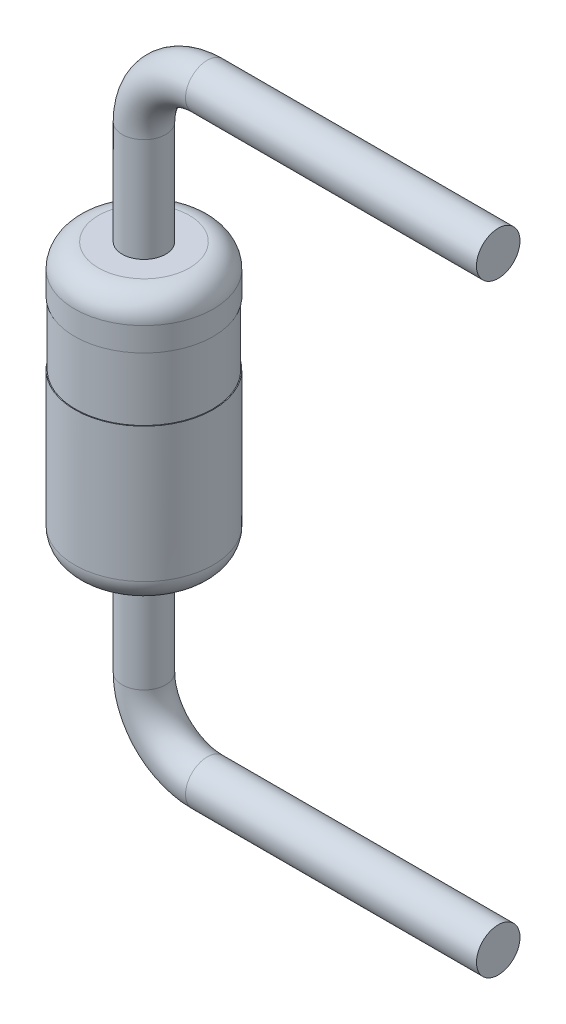
SolidWorks part; units mm, degrees
ref_plane "Plan de face" through (0, 0, 0) normal (0, 0, 1) x (1, 0, 0)
ref_plane "Plan de dessus" through (0, 0, 0) normal (0, 1, 0) x (1, 0, 0)
ref_plane "Plan de droite" through (0, 0, 0) normal (1, 0, 0) x (0, 0, -1)
sketch "Esquisse1" plane through (0, 0, 0) normal (0, 0, 1) x (1, 0, 0)
  line L0 (0, 0) -> (0.875, 0)
  line L6 (0.875, 1.7) -> (0, 1.7)
  line L7 (0, 1.7) -> (0, 0)
  line L8 (0.875, 1.7) -> (0.875, 0)
  dimension "D1" = 0.875
  dimension "D2" = 1.7
revolve "Révolution1" add sketch "Esquisse1" angle 360 about L7
fillet "Congé1" radius 0.3 1 edges at (-0.875, 1.7, 0)
sketch "Esquisse2" plane through (0, 0, 0) normal (0, 0, 1) x (1, 0, 0)
  line L0 (0, 1.7) -> (0, 3.01)
  line L1 (0.575, 1.7) -> (-0.575, 1.7) construction
  line L2 (0.8, 3.81) -> (4.475, 3.81)
  line L3 (0.875, 0) -> (0.875, 1.4) construction
  arc A0 (0, 3.01) -> (0.8, 3.81) centre (0.8, 3.01) cw
  dimension "D3" = 0.8
  dimension "D1" = 3.6
  dimension "D2" = 3.81
sketch "Esquisse3" plane through (0, 1.7, 0) normal (0, 1, 0) x (1, 0, 0)
  circle A0 centre (0, 0) radius 0.275
  dimension "D1" = 0.55
sweep "Balayage1" add profiles "Esquisse3" path "Esquisse2"
mirror "Symétrie1" of "Balayage1", "Congé1", "Révolution1"
sketch "Esquisse4" plane through (0, 0, 0) normal (0, 0, 1) x (1, 0, 0)
  line L0 (-0.875, 1.4) -> (-0.875, -1.4) construction
  line L1 (-0.875, 1.1) -> (-0.865, 1.1)
  line L2 (-0.875, 1.1) -> (-0.875, 0.3)
  line L3 (-0.875, 0.3) -> (-0.865, 0.3)
  line L4 (-0.865, 1.1) -> (-0.865, 0.3)
  line L5 (0.575, 1.7) -> (-0.575, 1.7) construction
  dimension "D1" = 0.6
  dimension "D2" = 0.8
  dimension "D3" = 0.01
revolve "Enlèvement de matière-Révolution1" cut sketch "Esquisse4" angle 360
